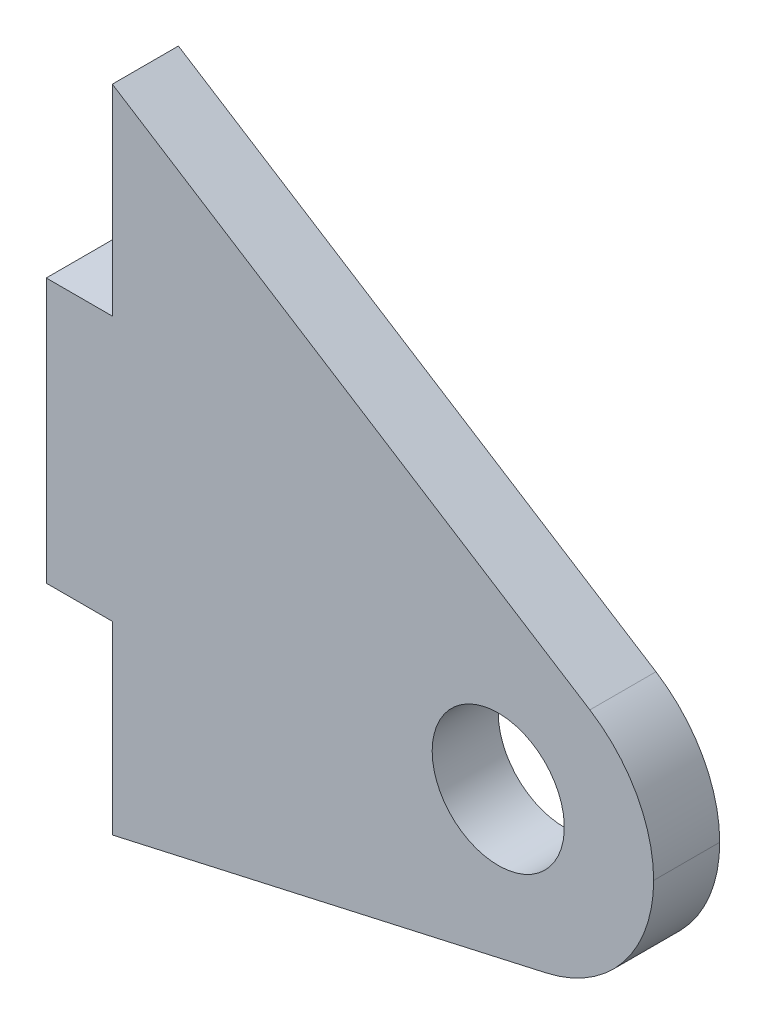
SolidWorks part; units mm, degrees
material "AISI 4340 Steel, annealed"
ref_plane "X-Y Datum" through (0, 0, 0) normal (0, 0, 1) x (1, 0, 0)
ref_plane "X-Z Datum" through (0, 0, 0) normal (0, 1, 0) x (1, 0, 0)
ref_plane "Y-Z Datum" through (0, 0, 0) normal (1, 0, 0) x (0, 0, -1)
sketch "Sketch1" plane through (0, 0, 0) normal (0, 0, 1) x (1, 0, 0)
  line L0 (0, 0) -> (0, 50000) construction
  line L1 (0, 0) -> (50000, 0) construction
  line L2 (68.5482, 0) -> (68.5482, 64.9121)
  line L3 (68.5482, 64.9121) -> (0, 64.9121)
  line L4 (0, 64.9121) -> (0, 0)
  line L5 (0, 0) -> (68.5482, 0)
  dimension "D1" = 90
extrude "Boss-Extrude1" add sketch "Sketch1" along normal blind 3.175
hole_wizard "1/4 (0.25) Diameter Hole1" positions "Sketch2" profile "Sketch3" hole size "1/4" standard "ANSI Inch" end condition through all
sketch "Sketch2" plane through (0, 0, 0) normal (0, 0, -1) x (-1, 0, 0)
  line L0 (-68.5482, 64.9121) -> (0, 64.9121) construction
  line L1 (0, 64.9121) -> (0, 0) construction
  point P0 (-18.542, 44.8461)
  dimension "D1" = 20.066
  dimension "D2" = 18.542
sketch "Sketch3" plane through (18.542, 44.8461, 0) normal (1, 0, 0) x (0, 1, 0)
  line L0 (0, 0) -> (0, 3.175)
  line L1 (0, 3.175) -> (3.175, 3.175)
  line L2 (3.175, 3.175) -> (3.175, 0)
  line L5 (3.175, 0) -> (0, 0)
  line L11 (0, -6.35) -> (0, 107.95) construction
  dimension "Thru Hole Dia." = 6.35
  dimension "Thru Hole Depth" = 3.175
sketch "Sketch4" plane through (0, 0, 0) normal (0, 0, -1) x (-1, 0, 0)
  line L0 (0, 64.9121) -> (-26.0096, 48.4021)
  line L1 (-26.0096, 48.4021) -> (-26.0096, 39.5121)
  line L2 (-26.0096, 39.5121) -> (0, 33.6701)
  line L3 (0, 64.9121) -> (0, 0) construction
  line L4 (0, 33.6701) -> (0, 64.9121)
  line L5 (0, 28.0016) -> (0, 34.8233) construction
  line M6 (-68.5482, 0) -> (0, 0)
  line M7 (0, 0) -> (0, 64.9121)
  line M8 (0, 64.9121) -> (-68.5482, 64.9121)
  line M9 (-68.5482, 64.9121) -> (-68.5482, 0)
  dimension "D1" = 26.0096
  dimension "D2" = 31.242
  dimension "D3" = 8.89
  dimension "D4" = 16.51
extrude "Cut-Extrude1" cut sketch "Sketch4" against normal through all contours L2 L1 L0 M8 M9 M6 M7 region at (37.4212, 30.5076, 0)
fillet "Fillet1" radius 6.604 2 edges at (26.0096, 48.4021, 1.5875) (26.0096, 39.5121, 1.5875)
sketch "Sketch5" plane through (0, 0, 0) normal (0, 0, -1) x (-1, 0, 0)
  line L0 (0, 42.5601) -> (3.175, 42.5601)
  line L1 (0, 64.9121) -> (0, 33.6701) construction
  line L2 (3.175, 42.5601) -> (3.175, 55.2601)
  line L3 (3.175, 55.2601) -> (0, 55.2601)
  line L4 (0, 42.5601) -> (0, 55.2601)
  dimension "D1" = 3.175
  dimension "D2" = 12.7
  dimension "D3" = 8.89
extrude "Boss-Extrude2" add sketch "Sketch5" against normal blind 3.175
